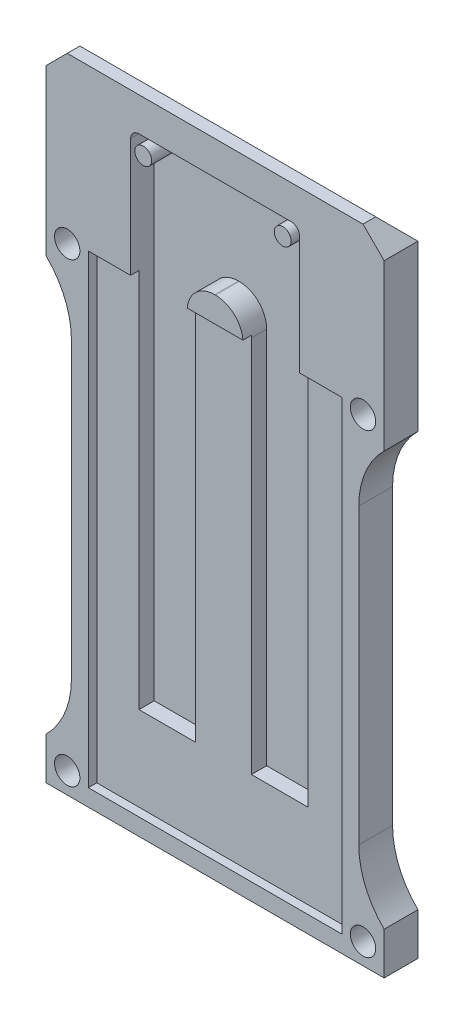
SolidWorks part; units mm, degrees
ref_plane "Alzado" through (0, 0, 0) normal (1, 0, 0) x (0, 1, 0)
ref_plane "Planta" through (0, 0, 0) normal (0, 0, 1) x (0, 1, 0)
ref_plane "Vista lateral" through (0, 0, 0) normal (0, 1, 0) x (-1, 0, 0)
sketch "Croquis2" plane through (0, 0, 0) normal (0, 0, 1) x (0, 1, 0)
  line L0 (-24.5, 20) -> (-24.5, 17)
  line L1 (-29.5, -20) -> (-24.5, -20)
  line L2 (-29.5, -20) -> (-29.5, 20)
  line L3 (-29.5, 20) -> (-24.5, 20)
  line L4 (29.5, -20) -> (29.5, 20)
  line L5 (-29.5, -20) -> (29.5, 20) construction
  line L6 (-29.5, 20) -> (29.5, -20) construction
  line L7 (-24.5, 17) -> (24.5, 17)
  line L8 (24.5, 17) -> (24.5, 20)
  line L9 (-24.5, -20) -> (-24.5, -17)
  line L10 (-24.5, -17) -> (24.5, -17)
  line L11 (24.5, -17) -> (24.5, -20)
  line L12 (24.5, 20) -> (29.5, 20)
  line L13 (24.5, -20) -> (29.5, -20)
  line L14 (29.5, -15) -> (42.5, -15)
  line L15 (-27.5, -15) -> (27.5, -15)
  line L16 (-27.5, -15) -> (-27.5, 15)
  line L17 (-27.5, 15) -> (27.5, 15)
  line L18 (27.5, -15) -> (27.5, 15)
  line L19 (-27.5, -15) -> (27.5, 15) construction
  line L20 (-27.5, 15) -> (27.5, -15) construction
  line L21 (42.5, -9) -> (42.5, 9)
  line L22 (42.5, 15) -> (29.5, 15)
  line L23 (-17.5, -15) -> (-17.5, 15)
  line L24 (29.5, -20) -> (46.5, -20)
  line L25 (46.5, -20) -> (46.5, 20)
  line L26 (46.5, 20) -> (29.5, 20)
  line L27 (41.5, 10) -> (-17.5, 10)
  line L28 (41.5, -10) -> (-17.5, -10)
  line L29 (0, 0) -> (-17.5, 0) construction
  line L30 (30.5, -0.05) -> (30.5, 0.05)
  line L31 (27.25, 3.3) -> (-17.5, 3.3)
  line L32 (27.25, -3.3) -> (-17.5, -3.3)
  line L34 (42.5, 9) -> (42.5, 15)
  line L35 (42.5, -9) -> (42.5, -15)
  circle A0 centre (27, 17.5) radius 1.5
  circle A2 centre (-27, -17.5) radius 1.5
  circle A3 centre (-27, 17.5) radius 1.5
  circle A4 centre (27, -17.5) radius 1.5
  arc A5 (27.25, 3.3) -> (30.5, 0.05) centre (27.25, 0.05) cw
  arc A6 (27.25, -3.3) -> (30.5, -0.05) centre (27.25, -0.05) ccw
  arc A7 (41.5, -10) -> (42.5, -9) centre (41.5, -9) ccw
  arc A8 (41.5, 10) -> (42.5, 9) centre (41.5, 9) cw
  circle A9 centre (40.5, 8.5) radius 1
  circle A10 centre (40.5, -8) radius 1
  point P0 (0, 0)
  point P14 (0, 0)
  point P19 (-24.5, 18.5)
  point P20 (-27, 17.5)
  point P21 (27, 17.5)
  point P22 (27, -17.5)
  point P23 (-27, -17.5)
  dimension "D10" = 3
  dimension "D12" = 60
  dimension "D18" = 3.25
  dimension "D19" = 1
  dimension "D20" = 2
  dimension "D1" = 59
  dimension "D2" = 40
  dimension "D3" = 2
  dimension "D4" = 5
  dimension "D5" = 30
  dimension "D6" = 2.5
  dimension "D7" = 2.5
  dimension "D8" = 2.5
  dimension "D9" = 2.5
  dimension "D11" = 55
  dimension "D13" = 10
  dimension "D14" = 4
  dimension "D15" = 20
  dimension "D16" = 48
  dimension "D17" = 6.6
  dimension "D21" = 1.5
  dimension "D22" = 2
  dimension "D23" = 2
extrude "Saliente-Extruir4" add sketch "Croquis2" along normal blind 4 contours L4 L28 L18 L15 L16 L17 L27 L12 L8 L7 L0 L3 L2 L1 L9 L10 L11 L13 A4 A3 A2 A0 | L21 L35 L14 L4 L24 L25 L26 L22 L34 | A9 | A10 | A7 L28 L4 L14 L35 | L27 A8 L34 L22 L4 | L18 A6 L4 A5 | L4 A6 L30 A5 region at (-18.5, -25.2128, 0) region at (-19.5654, 38, 0) region at (-12.491, 36.0207, 0) region at (0, 29.9086, 0) region at (0, 28.4514, 0) region at (12.491, 36.0207, 0) region at (-8.5, 40.5, 0) region at (8, 40.5, 0)
extrude "Saliente-Extruir5" add sketch "Croquis2<7>" along normal blind 3 contours L15 L23 L17 L16 | L27 L18 L17 L23 | L32 A6 L18 A5 L31 L23 | L18 L28 L23 L15 region at (-12.5, 5, 0) region at (0, 4.9999, 0) region at (0, -22.5, 0) region at (12.5, 5, 0)
sketch "Croquis2<7>" plane through (0, 0, 0) normal (0, 0, 1) x (0, 1, 0) same geometry as "Croquis2"
extrude "Saliente-Extruir6" add sketch "Croquis2<8>" along normal blind 1.2 contours L31 A5 L18 L27 L23 | L18 A5 L4 L27 | A8 L27 L4 A5 L30 A6 L28 A7 L21 A10 A9 | A6 L18 L28 L4 | A6 L32 L23 L28 L18 region at (0.0063, 35.9574, 0) region at (-6.4865, 28.5206, 0) region at (-6.65, 5.0001, 0) region at (6.4865, 28.5206, 0) region at (6.65, 5.0001, 0)
sketch "Croquis2<8>" plane through (0, 0, 0) normal (0, 0, 1) x (0, 1, 0) same geometry as "Croquis2"
fillet "Redondeo2" radius 10 4 edges at (17, -24.5, 2) (17, 24.5, 2) (-17, -24.5, 2) (-17, 24.5, 2)
chamfer "Chaflán2" distance 2.5 angle 45 3 edges at (-20, 46.5, 2) (20, 46.5, 2) (0, 46.5, 0)
